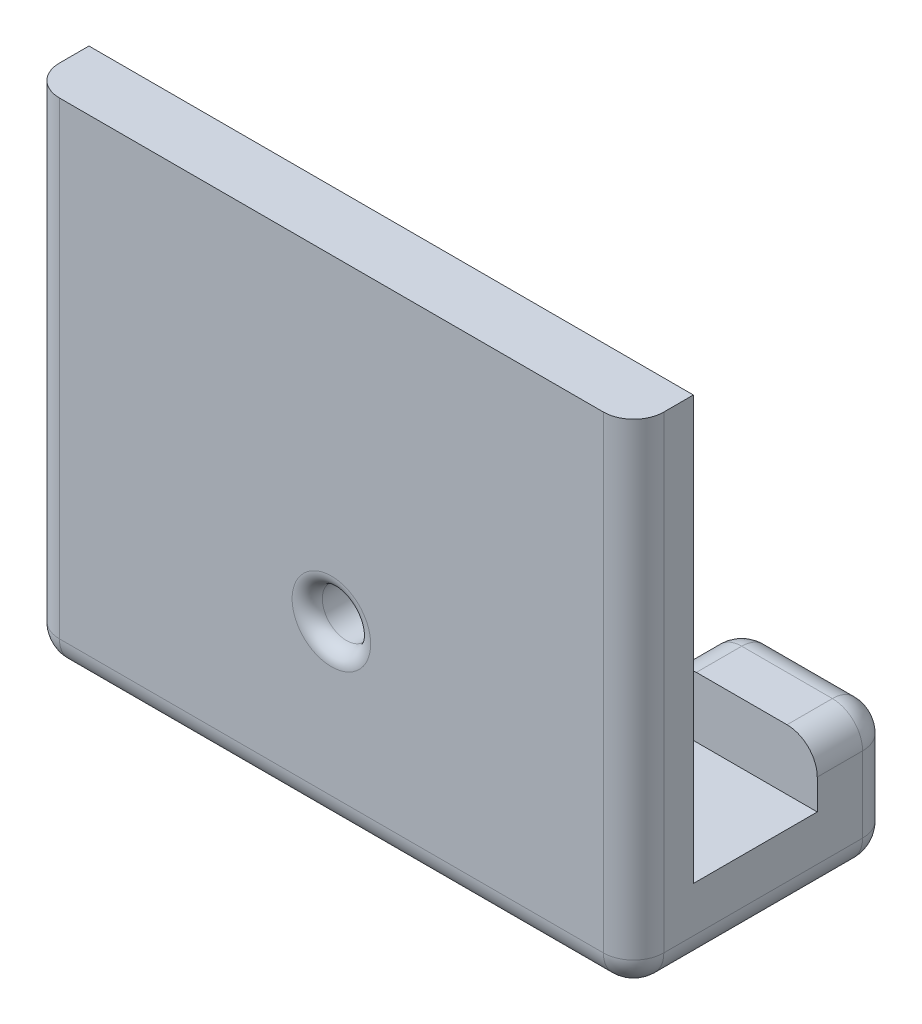
SolidWorks part; units mm, degrees
ref_plane "Front Plane" through (0, 0, 0) normal (0, 0, 1) x (1, 0, 0)
ref_plane "Top Plane" through (0, 0, 0) normal (0, 1, 0) x (1, 0, 0)
ref_plane "Right Plane" through (0, 0, 0) normal (1, 0, 0) x (0, 0, -1)
sketch "Sketch1" plane through (0, 0, 0) normal (0, 1, 0) x (1, 0, 0)
  line L0 (-44.6146, -25.9209) -> (-14.6146, -25.9209)
  line L1 (-14.6146, -35.876) -> (-44.6146, -35.876)
  line L2 (-4.6146, -23.7209) -> (-4.6146, -35.876)
  line L3 (-44.6146, -23.7209) -> (-34.6146, -23.7209)
  line L4 (-34.6146, -25.9209) -> (-34.6146, -18.7209)
  line L5 (-44.6146, -18.7209) -> (-34.6146, -18.7209)
  line L6 (-44.6146, -18.7209) -> (-44.6146, -30.9209)
  line L7 (-4.6146, -35.876) -> (-14.6146, -35.876)
  line L8 (-14.6146, -18.7209) -> (-14.6146, -30.9209)
  line L9 (-4.6146, -23.7209) -> (-4.6146, -18.7209)
  line L10 (-4.6146, -18.7209) -> (-14.6146, -18.7209)
  line L11 (-44.6146, -35.876) -> (-44.6146, -30.9209)
  line L12 (-14.6146, -30.9209) -> (-14.6146, -35.876)
  line L13 (-4.6146, -31.876) -> (-14.6146, -31.876)
  line L14 (-14.6146, -25.9209) -> (-4.6146, -25.9209)
  line L15 (-14.6146, -23.7209) -> (-4.6146, -23.7209)
  line L16 (-14.6146, -31.876) -> (-44.6146, -31.876)
extrude "Boss-Extrude1" add sketch "Sketch1" along normal blind 5 contours L8 L0 L6 | L8 L15 L9 L0 | L3 L6 L0 L4 | L12 L11 | L16 L11 | L2 L13 L12 L7 | L14 L8 L12 L13 L2 | L15 L8 L14 L2 | L5 L6 L3 L4 region at (-39.6146, 0, 24.8209) region at (-29.6146, 0, 28.8984) region at (-39.6146, 0, 21.2209) region at (-9.6146, 0, 28.8984) region at (-9.6146, 0, 24.8209) region at (-29.6146, 0, 33.876) region at (-9.6146, 0, 21.2209) region at (-9.6146, 0, 33.876)
extrude "Boss-Extrude2" add sketch "Sketch1<3>" along normal blind 9 contours L5 L6 L0 L4 | L8 L15 L9 L10 region at (-39.6146, 0, 21.2209) region at (-9.6146, 0, 21.2209)
sketch "Sketch1<3>" plane through (0, 0, 0) normal (0, 1, 0) x (1, 0, 0) same geometry as "Sketch1"
sketch "Sketch2" plane through (0, 5, 0) normal (0, 1, 0) x (1, 0, 0)
  line L0 (-4.6146, -35.876) -> (-4.6146, -31.9209)
  line L4 (-44.6146, -31.9209) -> (-44.6146, -35.876)
  line L5 (-44.6146, -31.9209) -> (-4.6146, -31.9209)
  line L6 (-44.6146, -35.876) -> (-4.6146, -35.876)
  line L8 (-44.6146, -35.876) -> (-4.6146, -35.876)
  line L10 (-44.6146, -31.9209) -> (-44.6146, -35.876)
  line M3 (-44.6146, -23.7209) -> (-44.6146, -35.876)
  line M32 (-44.6146, -35.876) -> (-4.6146, -35.876)
  line M37 (-4.6146, -35.876) -> (-4.6146, -23.7209)
extrude "Boss-Extrude4" add sketch "Sketch2" along normal blind 28 contours L5 M3 M32 M37 region at (-24.6146, 5, 33.8984)
fillet "Fillet1" radius 2 21 edges at (-14.6146, 9, 21.2209) (-44.6146, 4.5, 18.7209) (-4.6146, 9, 21.2209) (-4.6146, 16.5, 35.876) (-24.6146, 0, 35.876) (-44.6146, 16.5, 35.876) (-44.6146, 0, 27.2984) (-4.6146, 0, 27.2984) (-44.6146, 9, 21.2209) (-34.6146, 9, 21.2209) (-4.6146, 4.5, 18.7209) (-9.6146, 9, 18.7209) (-34.6146, 4.5, 18.7209) (-39.6146, 9, 18.7209) (-9.6146, 0, 18.7209) (-14.6146, 4.5, 18.7209) (-39.6146, 0, 18.7209) (-34.6146, 0, 22.3209) (-14.6146, 0, 22.3209) (-24.6146, 5, 25.9209) (-24.6146, 0, 25.9209)
sketch "Sketch6" plane through (0, 0, 31.9209) normal (0, 0, -1) x (-1, 0, 0)
  line L0 (24.6146, 5) -> (24.6146, 12)
  line L1 (44.6146, 5) -> (4.6146, 5) construction
  circle A0 centre (24.6146, 12) radius 1.6
extrude "Cut-Extrude1" cut sketch "Sketch6" against normal up to surface (3.9551 mm away) contours A0 region at (-25.714, 10.9006, 31.9209) up to face at (-24.6146, 17.5, 35.876)
fillet "Fillet2" radius 1 2 edges at (-23.0146, 12, 35.876) (-26.2146, 12, 31.9209)
